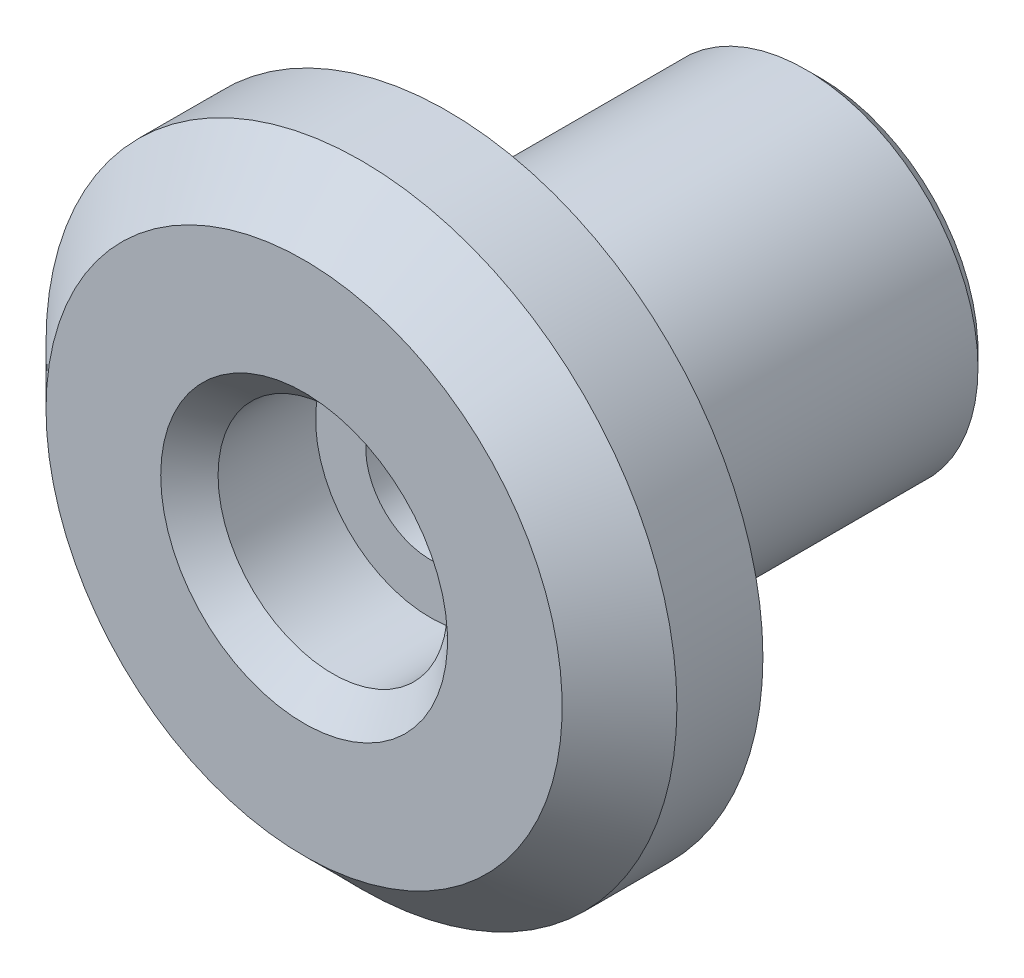
SolidWorks part; units mm, degrees
material "AISI 316 (1.4401)"
ref_plane "Płaszczyzna przednia" through (0, 0, 0) normal (0, 0, 1) x (1, 0, 0)
ref_plane "Płaszczyzna górna" through (0, 0, 0) normal (0, 1, 0) x (1, 0, 0)
ref_plane "Płaszczyzna prawa" through (0, 0, 0) normal (1, 0, 0) x (0, 0, -1)
sketch "Szkic1" plane through (0, 0, 0) normal (1, 0, 0) x (0, 0, -1)
  line L0 (0, 0) -> (18, 0) construction
  line L1 (18, 0) -> (18, 6)
  line L2 (18, 6) -> (5, 6)
  line L3 (5, 6) -> (5, 11)
  line L4 (5, 11) -> (0, 11)
  line L5 (0, 11) -> (0, 0)
  line L6 (0, 0) -> (18, 0)
  dimension "D1" = 12
  dimension "D2" = 13
  dimension "D3" = 5
  dimension "D4" = 22
revolve "Obrót1" add sketch "Szkic1" angle 360 about L0
chamfer "Sfazowanie1" distance 2 angle 45 1 edges at (11, 0, 0)
hole_wizard "Pogłębienie walcowe pod M4 Wkręt z łbem walcowym z gniazdem sześciokątnym1" positions "Szkic2" profile "Szkic3" counterbore size "M4" standard "DIN" end condition up to next
sketch "Szkic2" plane through (0, 0, 0) normal (0, 0, 1) x (1, 0, 0)
  point P0 (0, 0)
sketch "Szkic3" plane through (0, 0, 0) normal (1, 0, 0) x (0, -1, 0)
  line L0 (0, 0) -> (0, 18)
  line L1 (0, 18) -> (2.25, 18)
  line L3 (2.25, 18) -> (2.25, 4.4)
  line L4 (2.25, 4.4) -> (4, 4.4)
  line L5 (4, 4.4) -> (4, 0)
  line L7 (4, 0) -> (0, 0)
  line L11 (0, -6.35) -> (0, 107.95) construction
  dimension "Średnica otworu na wylot" = 4.5
  dimension "Głębokość otworu na wylot" = 18
  dimension "Średnica pogłębienia walcowego" = 8
  dimension "Głębokość pogłębienia walcowego" = 4.4
chamfer "Sfazowanie2" distance 1 angle 45 1 edges at (4, 0, 0)
sketch "Szkic4" plane through (0, 0, 0) normal (1, 0, 0) x (0, 0, -1)
  line L0 (7, 6) -> (6.7464, 5.8536)
  line L1 (18, 6) -> (5, 6) construction
  line L2 (6.5464, 5.8) -> (5.2, 5.8)
  line L3 (5, -11) -> (5, 11) construction
  line L4 (4.8, 6.2) -> (4.8, 6.2505)
  line L5 (4.8, 6.2505) -> (5, 6.8)
  line L6 (5, 6.8) -> (7, 6)
  line L7 (0, 0) -> (18, 0) construction
  line L8 (0, 9) -> (0, -9) construction
  line L9 (18, -6) -> (18, 6) construction
  arc A0 (6.7464, 5.8536) -> (6.5464, 5.8) centre (6.5464, 6.2) cw
  arc A1 (5.2, 5.8) -> (4.8, 6.2) centre (5.2, 6.2) cw
  dimension "D4" = 0.4
  dimension "D1" = 2
  dimension "D2" = 30
  dimension "D3" = 0.2
  dimension "D5" = 0.2
  dimension "D6" = 20
  dimension "D7" = 1
revolve "Wycięcie-obrót1" cut sketch "Szkic4" angle 360 about L7
chamfer "Sfazowanie3" distance 0.5 angle 45 1 edges at (6, 0, -18)
